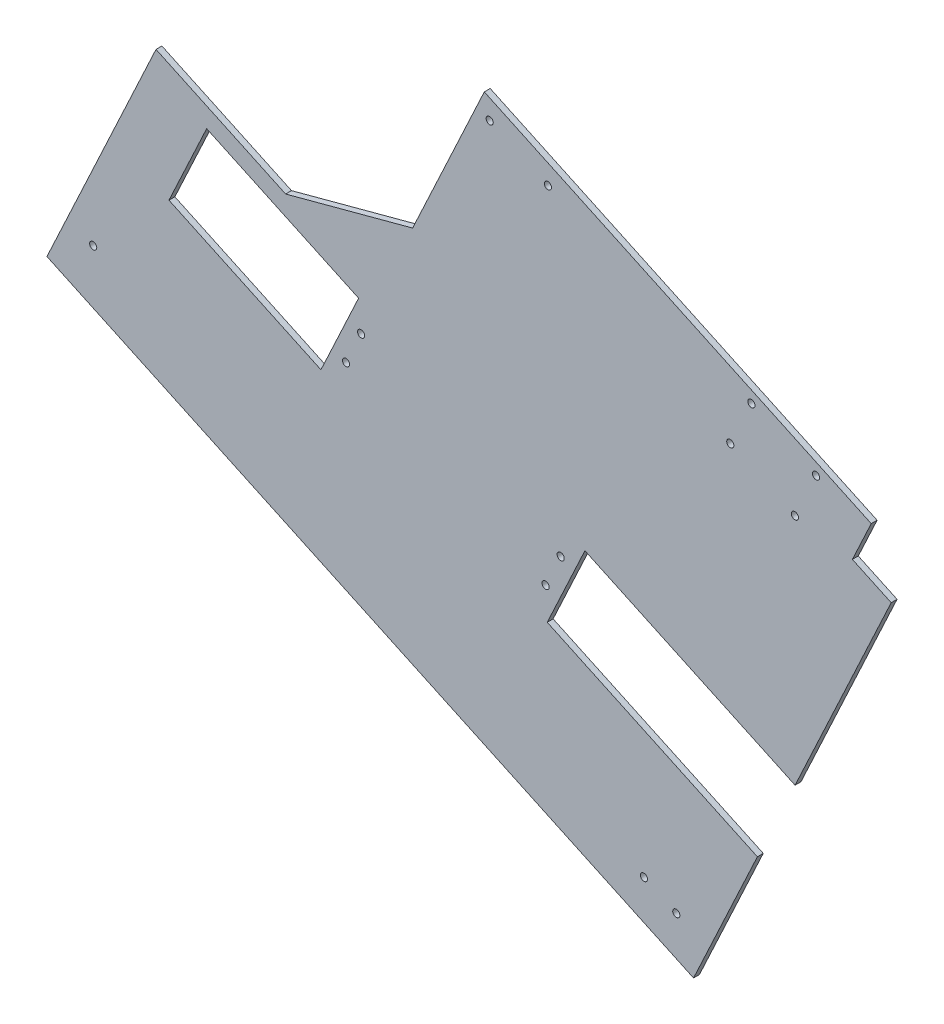
SolidWorks part; units mm, degrees
material "Balsa"
ref_plane "Front Plane" through (0, 0, 0) normal (0, 0, 1) x (1, 0, 0)
ref_plane "Top Plane" through (0, 0, 0) normal (0, 1, 0) x (1, 0, 0)
ref_plane "Right Plane" through (0, 0, 0) normal (1, 0, 0) x (0, 0, -1)
sketch "Sketch1" plane through (0, 0, 0) normal (0, 0, 1) x (1, 0, 0)
  line L0 (-299.6433, -82.65) -> (-127.3464, -36.4832)
  line L1 (-127.3464, -36.4832) -> (-87.1479, 49.7228)
  line L2 (-87.1479, 49.7228) -> (129.7831, -51.4338)
  line L3 (129.7831, -51.4338) -> (119.2177, -74.0915)
  line L4 (119.2177, -74.0915) -> (140.969, -84.2344)
  line L5 (140.969, -84.2344) -> (30.1585, -321.8683)
  line L6 (30.1585, -321.8683) -> (-332.3646, -152.8209)
  line L7 (-332.3646, -152.8209) -> (-299.6433, -82.65)
  line L9 (-332.3646, -152.8209) -> (-261.0998, 0.0069) construction
  line L10 (30.1585, -321.8683) -> (-332.3646, -152.8209) construction
  line L11 (140.969, -84.2344) -> (30.1585, -321.8683) construction
  line L12 (-189.2372, 97.3278) -> (129.7831, -51.4338) construction
  line L13 (119.2177, -74.0915) -> (140.969, -84.2344) construction
  line L14 (129.7831, -51.4338) -> (119.2177, -74.0915) construction
  line L15 (-110.3324, 0.0035) -> (-87.1479, 49.7228) construction
  line L17 (-198.5484, -55.5617) -> (-5.3632, -3.7979) construction
  line L18 (-198.5484, -55.5617) -> (-271.2117, -21.6782)
  line L19 (-271.2117, -21.6782) -> (-299.6433, -82.65)
  line L20 (-271.2117, -21.6782) -> (-198.5484, -55.5617) construction
  circle A0 centre (87.0035, -69.0002) radius 2
  circle A1 centre (98.8369, -43.6236) radius 2
  circle A2 centre (62.5845, -26.7189) radius 2
  circle A3 centre (50.7512, -52.0955) radius 2
  circle A4 centre (2.3586, -286.8374) radius 2
  circle A5 centre (-306.4229, -134.5749) radius 2
  circle A6 centre (20.4847, -295.2897) radius 2
  circle A7 centre (2.3586, -286.8374) radius 2 construction
  circle A8 centre (20.4847, -295.2897) radius 2 construction
  point P51 (0, 0)
  dimension "D1" = 4
  dimension "D2" = 4
  dimension "D3" = 4
  dimension "D4" = 4
  dimension "D7" = 4
  dimension "D5" = 27.5
  dimension "D6" = 15.8
extrude "Boss-Extrude1" add sketch "Sketch1" along normal blind 3.3 contours L7 L6 L5 L4 L3 L2 L1 L0 A6 A5 A4 A3 A2 A1 A0 | L18 L19 L0 region at (-256.4678, -53.2966, 0) region at (-69.6087, -133.5527, 0)
sketch "Sketch2" plane through (0, 0, 3.3) normal (0, 0, -1) x (-1, 0, 0)
  line L2 (87.1479, 49.7228) -> (-129.7831, -51.4338) construction
  line L3 (127.3464, -36.4832) -> (87.1479, 49.7228) construction
  circle A0 centre (51.4966, 22.0645) radius 2
  circle A1 centre (84.1237, 37.2788) radius 2
  dimension "D1" = 4
  dimension "D2" = 4
  dimension "D3" = 10
  dimension "D4" = 36
  dimension "D5" = 10
  dimension "D6" = 8
extrude "Cut-Extrude1" cut sketch "Sketch2" along normal blind 10 contours A0 | A1 region at (-51.4966, 22.0645, 3.3) region at (-84.1237, 37.2788, 3.3)
sketch "Sketch5" plane through (0, 0, 0) normal (0, 0, 1) x (1, 0, 0)
  line L0 (65.9543, -245.104) -> (-51.8657, -190.1636)
  line L2 (-51.8657, -190.1636) -> (-30.7348, -144.8482)
  line L3 (-30.7348, -144.8482) -> (87.0852, -199.7886)
  line L4 (87.0852, -199.7886) -> (65.9543, -245.104)
  line L7 (119.2177, -74.0915) -> (140.969, -84.2344) construction
  line L8 (140.969, -84.2344) -> (30.1585, -321.8683) construction
  dimension "D1" = 130
  dimension "D2" = 127.5
  dimension "D3" = 50
extrude "Cut-Extrude2" cut sketch "Sketch5" along normal blind 10
sketch "Sketch6" plane through (0, 0, 3.3) normal (0, 0, 1) x (1, 0, 0)
  line L0 (-178.7488, -130.9971) -> (-157.6179, -85.6817)
  line L1 (-157.6179, -85.6817) -> (-242.8108, -45.9555)
  line L2 (-242.8108, -45.9555) -> (-263.9417, -91.2709)
  line L3 (-263.9417, -91.2709) -> (-178.7488, -130.9971)
  line L4 (-332.3646, -152.8209) -> (-271.2117, -21.6782) construction
  line L9 (65.9543, -245.104) -> (-51.8657, -190.1636) construction
  line L10 (-30.7348, -144.8482) -> (87.0852, -199.7886) construction
  dimension "D1" = 130
  dimension "D2" = 94
extrude "Cut-Extrude3" cut sketch "Sketch6" against normal blind 10
sketch "Sketch7" plane through (0, 0, 3.3) normal (0, 0, 1) x (1, 0, 0)
  circle A0 centre (-52.7985, -172.5711) radius 2
  circle A1 centre (-44.3462, -154.4449) radius 2
  circle A2 centre (-164.6725, -120.4034) radius 2
  circle A3 centre (-156.2202, -102.2772) radius 2
  circle A4 centre (-52.7985, -172.5711) radius 2 construction
  circle A5 centre (-44.3462, -154.4449) radius 2 construction
  circle A6 centre (-164.6725, -120.4034) radius 2 construction
  circle A7 centre (-156.2202, -102.2772) radius 2 construction
extrude "Cut-Extrude4" cut sketch "Sketch7" against normal blind 10
